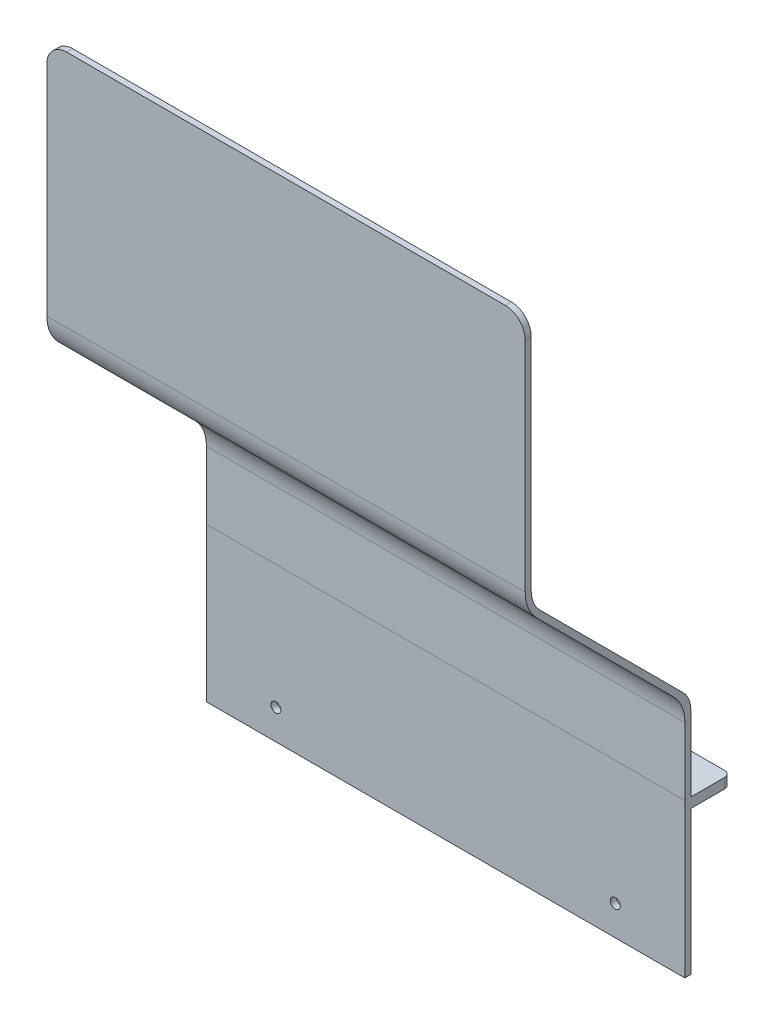
SolidWorks part; units mm, degrees
ref_plane "Front Plane" through (0, 0, 0) normal (0, 0, 1) x (1, 0, 0)
ref_plane "Top Plane" through (0, 0, 0) normal (0, 1, 0) x (1, 0, 0)
ref_plane "Right Plane" through (0, 0, 0) normal (1, 0, 0) x (0, 0, -1)
sketch "Sketch1" plane through (0, 0, 0) normal (0, 0, 1) x (1, 0, 0)
  line L1 (125, -36) -> (-125, -36)
  line L2 (125, -36) -> (125, 36)
  line L3 (125, 36) -> (-125, 36)
  line L4 (-125, -36) -> (-125, 36)
  line L5 (125, -36) -> (-125, 36) construction
  line L6 (125, 36) -> (-125, -36) construction
  point P0 (0, 0)
  dimension "D1" = 250
  dimension "D2" = 72
extrude "Boss-Extrude1" add sketch "Sketch1" along normal blind 3
sketch "Sketch2" plane through (0, 36, 0) normal (0, 1, 0) x (1, 0, 0)
  line L0 (-125, -3) -> (-125, 0) construction
  line L1 (-119.8, -3) -> (119.8, -3)
  line L2 (-119.8, -3) -> (-119.8, 20)
  line L3 (-119.8, 20) -> (119.8, 20)
  line L4 (119.8, -3) -> (119.8, 20)
  line L5 (125, -3) -> (125, 0) construction
  dimension "D1" = 5.2
  dimension "D2" = 23
  dimension "D3" = 5.2
extrude "Boss-Extrude2" add sketch "Sketch2" along normal blind 5
sketch "Sketch3" plane through (0, 41, 0) normal (0, 1, 0) x (1, 0, 0)
  line L0 (0, -55) -> (0, 55) construction
  circle A0 centre (-65, 8.5) radius 2.5
  circle A1 centre (65, 8.5) radius 2.5
  dimension "D1" = 65
extrude "Cut-Extrude1" cut sketch "Sketch3" against normal blind 5
fillet "Fillet1" radius 3 2 edges at (119.8, 38.5, -20) (-119.8, 38.5, -20)
sketch "Sketch4" plane through (0, 0, 3) normal (0, 0, 1) x (1, 0, 0)
  line L0 (-125, -36) -> (125, -36) construction
  line L1 (-125, 36) -> (-125, -36) construction
  line L2 (0, -55) -> (0, 55) construction
  circle A0 centre (-85, -21) radius 2.5
  circle A1 centre (85, -21) radius 2.5
  dimension "D1" = 15
  dimension "D2" = 40
extrude "Cut-Extrude2" cut sketch "Sketch4" against normal blind 5
sketch "Sketch6" plane through (0, 0, 3) normal (0, 0, 1) x (1, 0, 0)
  line L0 (-125, -36) -> (125, -36) construction
  line L1 (-125, 36) -> (-119.8, 36)
  line L2 (-125, 36) -> (-125, -36)
  line L3 (-125, -36) -> (-119.8, -36)
  line L4 (-119.8, 36) -> (-119.8, -36)
  line L5 (-119.8, 41) -> (-119.8, 36) construction
  line L6 (0, -12.65) -> (0, 12.65) construction
  line L7 (119.8, 36) -> (119.8, -36)
  line L8 (125, -36) -> (119.8, -36)
  line L9 (125, 36) -> (125, -36)
  line L10 (125, 36) -> (119.8, 36)
  dimension "D1" = 0
extrude "Cut-Extrude3" cut sketch "Sketch6" against normal blind 5
sketch "Sketch7" plane through (-119.8, 0, 0) normal (-1, 0, 0) x (0, 0, 1)
  line L0 (0, 41) -> (0, 74.7157)
  line L1 (-17, 41) -> (3, 41) construction
  line L2 (0, 41) -> (3, 41)
  line L3 (3, 41) -> (2.9165, 74.7157)
  line L4 (8.7744, 88.8579) -> (77.0586, 157.1421)
  line L5 (82.9165, 171.2843) -> (82.9165, 280.7033)
  line L6 (77.0586, 157.1421) -> (74.9373, 159.2635)
  line L7 (74.9373, 159.2635) -> (6.2562, 90.5824)
  line L8 (8.7744, 88.8579) -> (6.653, 90.9792)
  line L9 (6.2562, 90.5824) -> (3.8036, 88.1298)
  line L10 (0, 78.947) -> (0, 74.7157)
  line L11 (74.9373, 159.2635) -> (75.5231, 159.8492)
  line L12 (82.9165, 280.7033) -> (79.9165, 280.7033)
  line L13 (79.9165, 280.7033) -> (79.9165, 170.4558)
  arc A0 (8.7744, 88.8579) -> (2.9165, 74.7157) centre (22.9165, 74.7157) ccw construction
  arc A1 (77.0586, 157.1421) -> (82.9165, 171.2843) centre (62.9165, 171.2843) ccw construction
  arc A2 (75.5231, 159.8492) -> (79.9165, 170.4558) centre (64.9165, 170.4558) ccw
  arc A3 (0, 78.947) -> (3.8036, 88.1298) centre (12.9864, 78.947) cw
  spline S0 degree 2 poles (2.9165, 74.7157) (3.0324, 82.952) (8.7744, 88.8579) knots 0 0 0 1 1 1
  spline S1 degree 2 poles (77.0586, 157.1421) (82.8006, 163.048) (82.9165, 171.2843) knots 0 0 0 1 1 1
  line M1 (3, 41) -> (-17, 41)
  dimension "D1" = 15
  dimension "D2" = 12.9864
extrude "Boss-Extrude3" add sketch "Sketch7" against normal blind 239.6 contours L8 L4 L6 L7 | L6 S1 L5 L12 L13 A2 L11 | L3 S0 L8 L7 L9 A3 L10 L0 M1 region at (-119.8, 66.9863, 2.152) region at (-119.8, 124.0607, 41.8558) region at (-119.8, 218.9886, 81.2149)
sketch "Sketch8" plane through (0, 0, 82.9165) normal (0, 0, 1) x (1, 0, 0)
  line L5 (-119.8, 280.7033) -> (119.8, 280.7033)
  line L6 (-119.8, 280.7033) -> (-119.8, 290.7033)
  line L7 (-119.8, 290.7033) -> (119.8, 290.7033)
  line L8 (119.8, 280.7033) -> (119.8, 290.7033)
  line M6 (119.8, 280.7033) -> (-119.8, 280.7033)
  dimension "D1" = 10
extrude "Boss-Extrude4" add sketch "Sketch8" against normal blind 3 contours L8 L7 L6 M6 region at (0, 285.7033, 82.9165)
fillet "Fillet3" radius 10 2 edges at (119.8, 290.7033, 81.4165) (-119.8, 290.7033, 81.4165)
